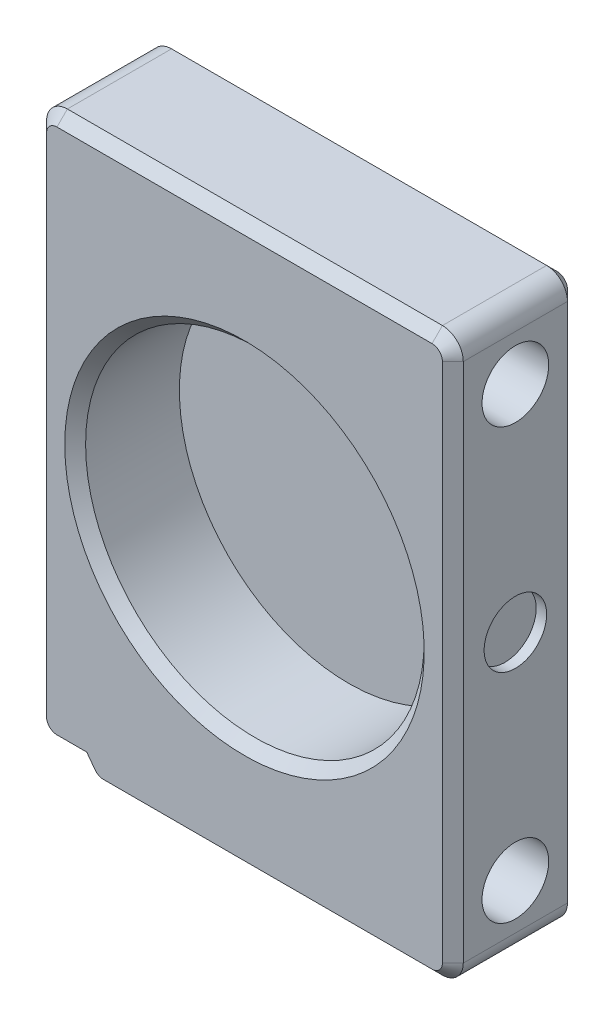
SolidWorks part; units mm, degrees
ref_plane "Front Plane" through (0, 0, 0) normal (0, 0, 1) x (1, 0, 0)
ref_plane "Top Plane" through (0, 0, 0) normal (0, 1, 0) x (1, 0, 0)
ref_plane "Right Plane" through (0, 0, 0) normal (1, 0, 0) x (0, 0, -1)
sketch "Sketch1" plane through (0, 0, 0) normal (0, 0, 1) x (1, 0, 0)
  line L0 (-10, 8.165) -> (10, 8.165) construction
  line L1 (-7.2698, -13.5) -> (10, -13.5)
  line L2 (-10, -12.7635) -> (-10, 13.5)
  line L3 (-10, 13.5) -> (10, 13.5)
  line L4 (10, -13.5) -> (10, 13.5)
  line L5 (-10, -13.5) -> (10, 13.5) construction
  line L6 (-10, 13.5) -> (10, -13.5) construction
  line L7 (10, 11.765) -> (-10, 11.765) construction
  line L8 (-10, -12.7635) -> (-7.8211, -12.7635)
  line L9 (-7.8211, -12.7635) -> (-7.2698, -13.5)
  line L12 (-10, -13.5) -> (-7.2698, -13.5) construction
  line L13 (-10, -13.5) -> (-10, -12.7635) construction
  circle A0 centre (0, 0) radius 8 construction
  point P0 (0, 0)
  dimension "D3" = 16
  dimension "D4" = 3.6
  dimension "D1" = 20
  dimension "D2" = 27
extrude "Boss-Extrude1" add sketch "Sketch1" along normal blind 6
sketch "Sketch2" plane through (0, 0, 6) normal (0, 0, 1) x (1, 0, 0)
  circle A0 centre (0, 0) radius 8.125
  dimension "D1" = 16.25
extrude "Cut-Extrude1" cut sketch "Sketch2" against normal blind 5
sketch "Sketch3" plane through (10, 0, 0) normal (1, 0, 0) x (0, 0, -1)
  line L0 (0, 0) -> (-6, 0) construction
  line L1 (-6, -13.5) -> (-6, 13.5) construction
  circle A0 centre (-3, 0) radius 1.5
  dimension "D1" = 3
extrude "Cut-Extrude2" cut sketch "Sketch3" against normal blind 0.5
sketch "Sketch4" plane through (10, 0, 0) normal (1, 0, 0) x (0, 0, -1)
  line L0 (-3, 13.5) -> (-3, 0) construction
  line L1 (-6, 13.5) -> (0, 13.5) construction
  line L2 (-3, 0) -> (0, 0) construction
  circle A0 centre (-3, 10.3154) radius 1.6
  circle A1 centre (-3, -10.3154) radius 1.6
  dimension "D1" = 3.2
  dimension "D2" = 20.6308
extrude "Cut-Extrude3" cut sketch "Sketch4" against normal through all
fillet "Fillet1" radius 1 5 edges at (-10, 13.5, 3) (10, 13.5, 3) (10, -13.5, 3) (-7.2698, -13.5, 3) (-10, -12.7635, 3)
chamfer "Chamfer1" distance 0.5 angle 45 23 edges at (8.125, 0, 6) (0, 13.5, 0) (-10, 0.3683, 0) (1.1154, -13.5, 0) (10, 0, 0) (1.1154, -13.5, 6) (-10, 0.3683, 6) (0, 13.5, 6) (10, 0, 6) (9.7071, -13.2071, 0) (9.7071, 13.2071, 0) (-9.7071, 13.2071, 0) (-9.7071, 13.2071, 6) (9.7071, 13.2071, 6) (9.7071, -13.2071, 6) (-8.4106, -12.7635, 0) (-7.6955, -12.9313, 0) (-7.6955, -12.9313, 6) (-8.4106, -12.7635, 6) (-7.2169, -13.3942, 0) (-7.2169, -13.3942, 6) (-9.7071, -12.4706, 0) (-9.7071, -12.4706, 6)
